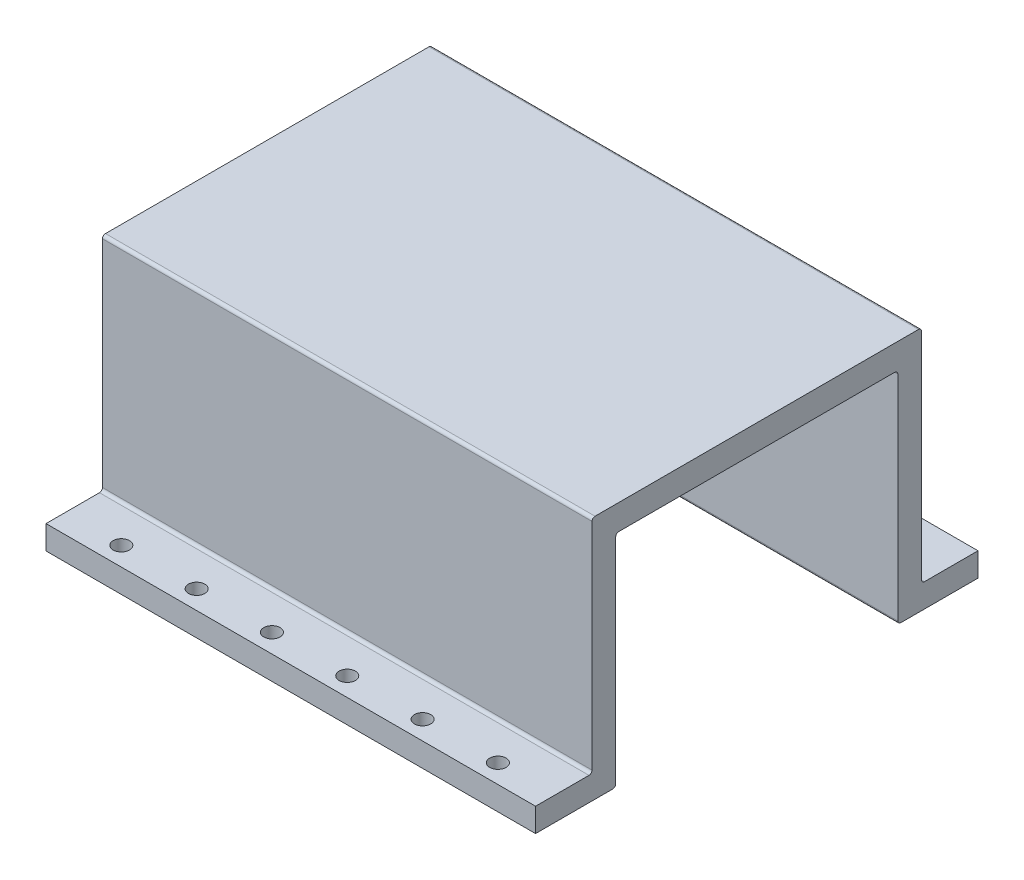
SolidWorks part; units mm, degrees
ref_plane "Front Plane" through (0, 0, 0) normal (0, 0, 1) x (1, 0, 0)
ref_plane "Top Plane" through (0, 0, 0) normal (0, 1, 0) x (1, 0, 0)
ref_plane "Right Plane" through (0, 0, 0) normal (1, 0, 0) x (0, 0, -1)
sketch "Sketch2" plane through (0, 0, 0) normal (1, 0, 0) x (0, 0, -1)
  line L0 (-74.6125, 0) -> (-55.5625, 0)
  line L1 (-55.5625, 0) -> (-55.5625, 74.676)
  line L2 (-55.5625, 74.676) -> (55.5625, 74.676)
  line L3 (55.5625, 74.676) -> (55.5625, 0)
  line L4 (55.5625, 0) -> (74.6125, 0)
  line L5 (74.6125, 0) -> (74.6125, -8)
  line L6 (74.6125, -8) -> (47.5625, -8)
  line L7 (47.5625, -8) -> (47.5625, 66.176)
  line L8 (47.5625, 66.176) -> (-47.5625, 66.176)
  line L9 (-47.5625, 66.176) -> (-47.5625, -8)
  line L10 (-47.5625, -8) -> (-74.6125, -8)
  line L11 (-74.6125, -8) -> (-74.6125, 0)
  line L12 (-91.9452, 74.676) -> (31.9599, 74.676) construction
  point P13 (0, 66.176)
  point P14 (0, 74.676)
  point P16 (55.499, 68.7335)
  point P18 (55.499, 0)
  point P19 (-65.0875, 0)
  dimension "D1" = 8.5
  dimension "D3" = 111.125
  dimension "D4" = 74.676
  dimension "D5" = 8
  dimension "D6" = 8
  dimension "D2" = 19.05
extrude "Boss-Extrude1" add sketch "Sketch2" along normal blind 50.8 and the other way blind 114.3 contours L1 L2 L3 L4 L5 L6 L7 L8 L9 L10 L11 L0
fillet "Fillet1" radius 1.016 8 edges at (-31.75, 66.176, -47.5625) (-31.75, 74.676, -55.5625) (-31.75, 74.676, 55.5625) (-31.75, 66.176, 47.5625) (-31.75, 0, -55.5625) (-31.75, -8, -47.5625) (-31.75, -8, 47.5625) (-31.75, 0, 55.5625)
sketch "Sketch4" plane through (0, 0, 0) normal (0, 1, 0) x (1, 0, 0)
  line L0 (-114.3, 68.2625) -> (50.8, 68.2625) construction
  line L1 (-114.3, 56.5785) -> (-114.3, 74.6125) construction
  line L2 (50.8, 56.5785) -> (50.8, 74.6125) construction
  line L4 (-95.25, 68.2625) -> (-95.25, 78.2625) construction
  line L5 (-127.0814, 55.5625) -> (79.4504, 55.5625) construction
  line L6 (50.8, 55.5625) -> (-114.3, 55.5625) construction
  line L7 (-95.25, 78.2625) -> (31.75, 78.2625) construction
  circle A0 centre (-95.25, 68.2625) radius 2.75
  circle A1 centre (-69.85, 68.2625) radius 2.75
  circle A2 centre (-44.45, 68.2625) radius 2.75
  circle A3 centre (-19.05, 68.2625) radius 2.75
  circle A4 centre (6.35, 68.2625) radius 2.75
  circle A5 centre (31.75, 68.2625) radius 2.75
  point P9 (-31.75, 68.2625)
  point P23 (0, 0)
  point P25 (-31.75, 78.2625)
  dimension "D2" = 5.5
  dimension "D4" = 25.4
  dimension "D1" = 12.7
  dimension "D5" = 10
  dimension "D6" = 127
  dimension "D3" = 6
extrude "Cut-Extrude1" cut sketch "Sketch4" against normal blind 101.6
mirror "Mirror1" about plane through (0, 0, 0) normal (0, 0, 1) of "Cut-Extrude1"
equation "\"D4@Sketch2\"=2.94in"
equation "\"D1@Boss-Extrude1\"=2in"
equation "\"D2@Sketch2\"=0.75in"
equation "\"D1@Fillet1\"=0.04in"
equation "\"D2@Boss-Extrude1\"=4.5in"
equation "\"D4@Sketch4\"=1in"
equation "\"D1@Sketch4\"=0.5in"
equation "\"D3@Sketch2\"=4.375in"
equation "\"D6@Sketch4\"=\"D4@Sketch4\"*(\"D3@Sketch4\"-1)"
